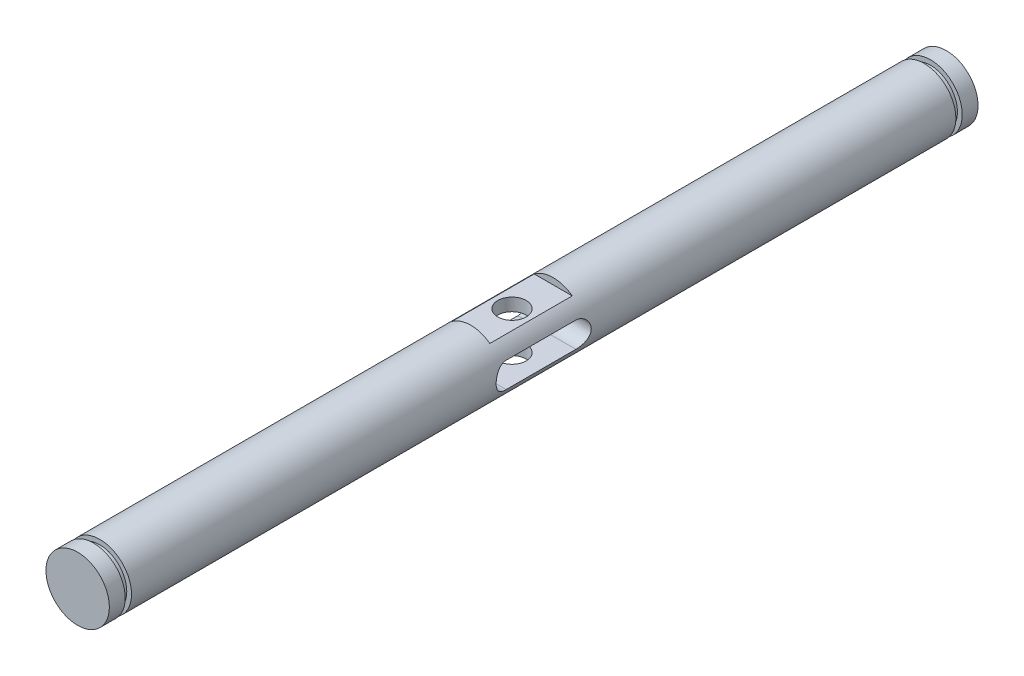
SolidWorks part; units mm, degrees
material "AISI 4340 Steel, normalized"
ref_plane "Front Plane" through (0, 0, 0) normal (0, 0, 1) x (1, 0, 0)
ref_plane "Top Plane" through (0, 0, 0) normal (0, 1, 0) x (1, 0, 0)
ref_plane "Right Plane" through (0, 0, 0) normal (1, 0, 0) x (0, 0, -1)
sketch "Sketch3" plane through (0, 0, 0) normal (0, 0, 1) x (1, 0, 0)
  circle A0 centre (0, 0) radius 10
extrude "Boss-Extrude1" add sketch "Sketch3" along normal blind 130 and the other way blind 130
sketch "Sketch4" plane through (0, 0, 130) normal (0, 0, 1) x (1, 0, 0)
  circle A0 centre (0, 0) radius 8.5
extrude "Boss-Extrude2" add sketch "Sketch4" along normal blind 2
sketch "Sketch5" plane through (0, 0, 132) normal (0, 0, 1) x (1, 0, 0)
  circle A0 centre (0, 0) radius 10
extrude "Boss-Extrude3" add sketch "Sketch5" along normal blind 5
sketch "Sketch6" plane through (0, 0, -130) normal (0, 0, -1) x (-1, 0, 0)
  circle A0 centre (0, 0) radius 8.5
extrude "Boss-Extrude4" add sketch "Sketch6" along normal blind 2
sketch "Sketch7" plane through (0, 0, -132) normal (0, 0, -1) x (-1, 0, 0)
  circle A0 centre (0, 0) radius 10
extrude "Boss-Extrude5" add sketch "Sketch7" along normal blind 5
sketch "Sketch8" plane through (0, 0, 0) normal (1, 0, 0) x (0, 0, -1)
  line L2 (-13, 8) -> (13, 8)
  line L3 (130, 10) -> (-130, 10) construction
  line L4 (-13, 10) -> (-13, 8)
  line L5 (13, 8) -> (13, 10)
  line L6 (13, 10) -> (-13, 10)
  line L7 (13, -8) -> (-13, -8)
  line L8 (13, -10) -> (13, -8)
  line L9 (-13, -8) -> (-13, -10)
  line L10 (-13, -10) -> (13, -10)
  line L11 (11, 4) -> (-11, 4)
  line L12 (11, -4) -> (-11, -4)
  arc A1 (11, 4) -> (11, -4) centre (11, 0) cw
  arc A2 (-11, 4) -> (-11, -4) centre (-11, 0) ccw
extrude "Cut-Extrude1" cut sketch "Sketch8" against normal through all both and the other way through all
sketch "Sketch9" plane through (0, 8, 0) normal (0, 1, 0) x (1, 0, 0)
  circle A0 centre (0, 0) radius 4.5
extrude "Cut-Extrude2" cut sketch "Sketch9" against normal through all
